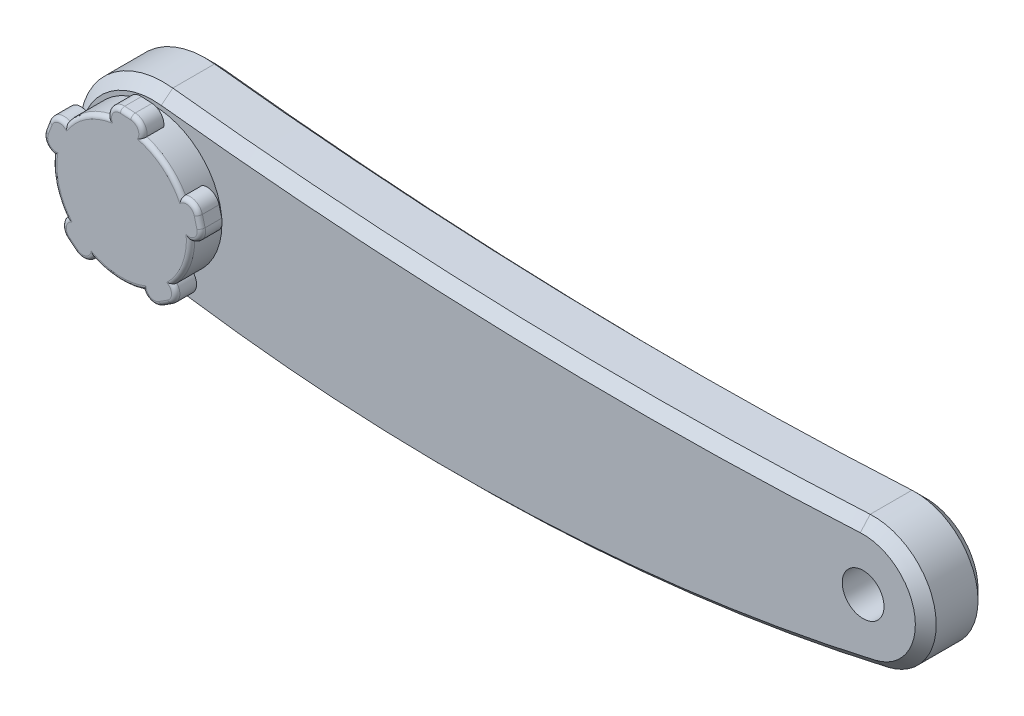
SolidWorks part; units mm, degrees
ref_plane "Front Plane" through (0, 0, 0) normal (0, 0, 1) x (1, 0, 0)
ref_plane "Top Plane" through (0, 0, 0) normal (0, 1, 0) x (1, 0, 0)
ref_plane "Right Plane" through (0, 0, 0) normal (1, 0, 0) x (0, 0, -1)
sketch "Sketch1" plane through (0, 0, 0) normal (0, 0, 1) x (1, 0, 0)
  line L0 (-85, 0) -> (85, 0) construction
  circle A0 centre (-85, 0) radius 20
  circle A1 centre (85, 0) radius 15
  arc A2 (-82.7465, 19.8726) -> (84.1861, 14.9779) centre (29.9265, 1013.5048) ccw
  arc A3 (-88.3618, -19.7154) -> (88.3697, -14.6166) centre (-12.7206, 423.8817) ccw
  point P4 (0, 0)
  dimension "D2" = 40
  dimension "D3" = 30
  dimension "D4" = 450
  dimension "D5" = 1000
  dimension "D1" = 170
extrude "Boss-Extrude1" add sketch "Sketch1" along normal mid plane 15 contours A0 | A0 L0 A1 A2 | L0 A0 A3 A1 | A1 region at (-1.0237, 7.6812, 0) region at (-72.4659, -14.8523, 0) region at (-0.4487, -12.3679, 0) region at (74.4175, 10.0231, 0)
chamfer "Chamfer1" distance 2.5 angle 45 8 edges at (99.8523, 2.0996, -7.5) (0.6174, 13.9344, -7.5) (-104.8018, 2.8087, -7.5) (0.2568, -25.9311, -7.5) (-104.8018, 2.8087, 7.5) (0.6174, 13.9344, 7.5) (99.8523, 2.0996, 7.5) (0.2568, -25.9311, 7.5)
sketch "Sketch2" plane through (0, 0, 7.5) normal (0, 0, 1) x (1, 0, 0)
  circle A0 centre (-85, 0) radius 16.5
  dimension "D1" = 33
extrude "Boss-Extrude2" add sketch "Sketch2" along normal mid plane 5
sketch "Sketch4" plane through (0, 0, 10) normal (0, 0, 1) x (1, 0, 0)
  line L2 (-66.0119, 3.7765) -> (-66.6676, 6.2235)
  line L3 (-71.0654, 8.0452) -> (-85, 0)
  line L4 (-85, 0) -> (-66.3397, 5) construction
  line L5 (-85, 0) -> (-68.9097, 0)
  line L6 (-85, 0) -> (-80.0278, -15.3028)
  line L7 (-75.5407, -16.8918) -> (-73.416, -15.512)
  line L8 (-73.0426, -10.7665) -> (-85, 0)
  line L9 (-85, 0) -> (-98.0173, -9.4577)
  line L10 (-98.142, -14.2161) -> (-96.1731, -15.8105)
  line L11 (-91.5445, -14.6992) -> (-85, 0)
  line L12 (-85, 0) -> (-98.0173, 9.4577)
  line L13 (-102.5814, 8.1057) -> (-103.4893, 5.7406)
  line L14 (-101.0022, 1.6819) -> (-85, 0)
  line L15 (-85, 0) -> (-80.0278, 15.3028)
  line L16 (-82.724, 19.2257) -> (-85.2539, 19.3583)
  line L17 (-88.3454, 15.7387) -> (-85, 0)
  arc A0 (-66.0119, 3.7765) -> (-68.9097, 0) centre (-68.9097, 3) cw
  arc A1 (-71.0654, 8.0452) -> (-66.6676, 6.2235) centre (-69.5654, 5.4471) cw
  arc A2 (-75.5407, -16.8918) -> (-80.0278, -15.3028) centre (-77.1746, -14.3758) cw
  arc A3 (-73.0426, -10.7665) -> (-73.416, -15.512) centre (-75.05, -12.996) cw
  arc A4 (-98.142, -14.2161) -> (-98.0173, -9.4577) centre (-96.254, -11.8847) cw
  arc A5 (-91.5445, -14.6992) -> (-96.1731, -15.8105) centre (-94.2852, -13.479) cw
  arc A6 (-102.5814, 8.1057) -> (-98.0173, 9.4577) centre (-99.7807, 7.0306) cw
  arc A7 (-101.0022, 1.6819) -> (-103.4893, 5.7406) centre (-100.6886, 4.6655) cw
  arc A8 (-82.724, 19.2257) -> (-80.0278, 15.3028) centre (-82.881, 16.2299) cw
  arc A9 (-88.3454, 15.7387) -> (-85.2539, 19.3583) centre (-85.4109, 16.3624) cw
  circle A10 centre (-85, 0) radius 2
  point P7 (-67.6795, 10)
  point P37 (-85, 0)
  circle M2 centre (-85, 0) radius 16.5
  dimension "D3" = 3
  dimension "D5" = 4
  dimension "D1" = 30
  dimension "D2" = 20
  dimension "D4" = 5
extrude "Boss-Extrude5" add sketch "Sketch4" along normal blind 5 contours L9 A10 L11 | L11 A10 L6 | L6 A10 L8 | L8 A10 L5 | L4 L5 A10 | L3 L4 A10 | L3 A10 L15 | L15 A10 L17 | L17 A10 L12 | L14 A10 L9 | A10 L9 A4 A5 L11 M2 | A10 L6 A2 A3 L8 M2 | A10 L15 A8 A9 L17 M2 | A9 A8 L16 M2 | A10 L4 A1 L3 M2 | L4 A10 L5 A0 M2 | L4 L2 A1 M2 | A10 L8 A3 A0 L5 M2 | A10 L11 A5 A2 L6 M2 | A10 L14 A7 A4 L9 M2 | A10 L17 A9 A6 L12 M2 | A10 L3 A1 A8 L15 M2 | L12 A6 L13 A7 L14 | L6 A2 L7 A3 L8 | L9 A4 L10 A5 L11 | L5 A0 L2 A1 L3 region at (-68.4431, 6.4563, 10) region at (-74.8271, -3.905, 10) region at (-73.9833, 1.4506, 10) region at (-74.734, 4.2521, 10) region at (-78.1425, 8.4683, 10) region at (-83.6818, 0.1735, 10) region at (-83.7717, 0.5088, 10) region at (-83.7829, -0.4672, 10) region at (-78.9998, -9.2394, 10) region at (-84.0756, 17.6395, 10) region at (-84.4234, 11.0017, 10) region at (-84.1796, 1.0132, 10) region at (-84.2821, -1.1055, 10) region at (-85.8295, -1.0244, 10) region at (-85.0682, -1.3019, 10) region at (-86.2593, -0.3374, 10) region at (-84.931, 1.3163, 10) region at (-85.71, 1.0934, 10) region at (-85.5703, -10.8817, 10) region at (-90.9347, 9.1387, 10) region at (-91.9331, -8.5616, 10) region at (-95.5254, -2.8203, 10)
fillet "Fillet1" radius 1 20 edges at (-87.5535, 18.4623, 15) (-83.9889, 19.292, 15) (-80.5307, 18.0943, 15) (-74.6162, 12.8229, 15) (-68.2303, 8.1337, 15) (-66.3397, 5, 15) (-66.4102, 1.3409, 15) (-69.5959, -5.9131, 15) (-72.0823, -13.4355, 15) (-74.4784, -16.2019, 15) (-77.9802, -17.2656, 15) (-85.8635, -16.4774, 15) (-93.7861, -16.4372, 15) (-97.1575, -15.0133, 15) (-99.2513, -12.0116, 15) (-100.9378, -4.2705, 15) (-103.3478, 3.2767, 15) (-103.0354, 6.9231, 15) (-100.8276, 9.842, 15) (-93.9865, 13.8381, 15)
sketch "Sketch5" plane through (0, 0, 7.5) normal (0, 0, 1) x (1, 0, 0)
  circle A0 centre (85, 0) radius 5
  dimension "D1" = 10
extrude "Cut-Extrude1" cut sketch "Sketch5" against normal blind 10 contours A0
sketch "Sketch6" plane through (0, 0, -7.5) normal (0, 0, -1) x (-1, 0, 0)
  circle A0 centre (85, 0) radius 5
  dimension "D1" = 10
extrude "Boss-Extrude6" add sketch "Sketch6" along normal blind 10
